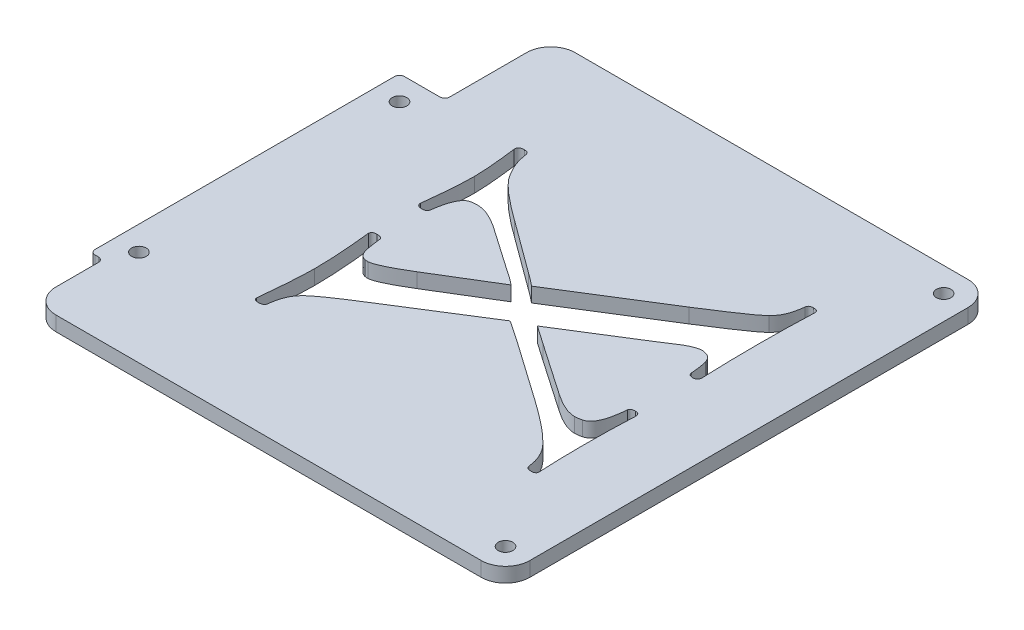
SolidWorks part; units mm, degrees
ref_plane "Front Plane" through (0, 0, 0) normal (0, 0, 1) x (1, 0, 0)
ref_plane "Top Plane" through (0, 0, 0) normal (0, 1, 0) x (1, 0, 0)
ref_plane "Right Plane" through (0, 0, 0) normal (1, 0, 0) x (0, 0, -1)
ref_plane "Plane1" through (0, 23, 0) normal (0, 1, 0) x (1, 0, 0)
sketch "Sketch1" plane through (0, 23, 0) normal (0, 1, 0) x (1, 0, 0)
  line L0 (98.3054, 50) -> (98.3054, 28.2195)
  line L1 (189, 50) -> (98.3054, 50)
  line L2 (189, 50) -> (189, -50)
  line L3 (189, -50) -> (97.6502, -50)
  line L5 (98.3054, 28.2195) -> (89, 28.2195)
  line L6 (89, 28.2195) -> (89, -35.308)
  line L7 (89, -35.308) -> (91.6598, -35.308)
  line L8 (91.6598, -35.308) -> (91.6598, -50)
  line L9 (91.6598, -50) -> (97.6502, -50)
  line L10 (94.8054, 33.2195) -> (98.3054, 33.2195) construction
  line L11 (184, 45) -> (184, 50) construction
  line L12 (93.3054, 31.7195) -> (93.3054, 28.2195) construction
  line L13 (99.4745, -35.308) -> (86.1225, -35.308) construction
  line L14 (88.1598, -40.308) -> (91.6598, -40.308) construction
  line L15 (86.6598, -38.808) -> (86.6598, -35.308) construction
  line L16 (189, 0) -> (190, 0) construction
  line L17 (190, -60) -> (190, 60) construction
  line L18 (105.0183, -40) -> (185.0183, -40) construction
  line L19 (105.0183, -40) -> (105.0183, 40) construction
  line L20 (105.0183, 40) -> (185.0183, 40) construction
  line L21 (185.0183, -40) -> (185.0183, 40) construction
  line L22 (184, 45) -> (189, 45) construction
  line L23 (184, -45) -> (189, -45) construction
  line L24 (184, -45) -> (184, -50) construction
  line L25 (94, 23.2195) -> (94, 28.2195) construction
  line L26 (94, 23.2195) -> (89, 23.2195) construction
  line L27 (94, -30.308) -> (94, -35.308) construction
  line L28 (94, -30.308) -> (89, -30.308) construction
  line L29 (190, -55) -> (190, 55) construction
  circle A0 centre (86.6598, -40.308) radius 1.5 construction
  circle A1 centre (93.3054, 33.2195) radius 1.5 construction
  circle A2 centre (184, 45) radius 1.5 construction
  circle A3 centre (184, 45) radius 1.5 construction
  circle A4 centre (184, -45) radius 1.5 construction
  circle A6 centre (94, 23.2195) radius 1.5 construction
  circle A7 centre (94, -30.308) radius 1.5 construction
  point P32 (185.0183, 0)
  point P53 (0, 0)
  dimension "D1" = 100
  dimension "D2" = 80
  dimension "D3" = 3.5
  dimension "D4" = 5
  dimension "D5" = 1
  dimension "D6" = 100
extrude "Boss-Extrude1" add sketch "Sketch1" along normal blind 3
fillet "Fillet3" radius 5 4 edges at (189, 24.5, -50) (98.3054, 24.5, -50) (91.6598, 24.5, 50) (189, 24.5, 50)
fillet "Fillet2" radius 1 4 edges at (89, 24.5, -28.2195) (98.3054, 24.5, -28.2195) (91.6598, 24.5, 35.308) (89, 24.5, 35.308)
sketch "Sketch2" plane through (0, 23, 0) normal (0, 1, 0) x (1, 0, 0)
  circle A0 centre (184, -45) radius 1.5 construction
  circle A1 centre (184, -45) radius 1.5
  circle A2 centre (94, -30.308) radius 1.5 construction
  circle A3 centre (94, -30.308) radius 1.5
  circle A4 centre (94, 23.2195) radius 1.5 construction
  circle A5 centre (94, 23.2195) radius 1.5
  circle A6 centre (184, 45) radius 1.5 construction
  circle A7 centre (184, 45) radius 1.5
extrude "Cut-Extrude1" cut sketch "Sketch2" along normal up to surface (3 mm away) up to face at (116.9913, 26, 1.7721)
sketch "Sketch4" plane through (0, 23, 0) normal (0, 1, 0) x (1, 0, 0)
  line L0 (176.5151, -28.0588) -> (176.5151, 28.0588) construction
  line L2 (150, 0) -> (182, 0) construction
  text T0 "X" font "@Yu Mincho Demibold" height 60
  point P3 (176.5151, 0)
extrude "Cut-Extrude2" cut sketch "Sketch4" along normal up to surface (3 mm away) up to face at (184, 26, 43.5)
